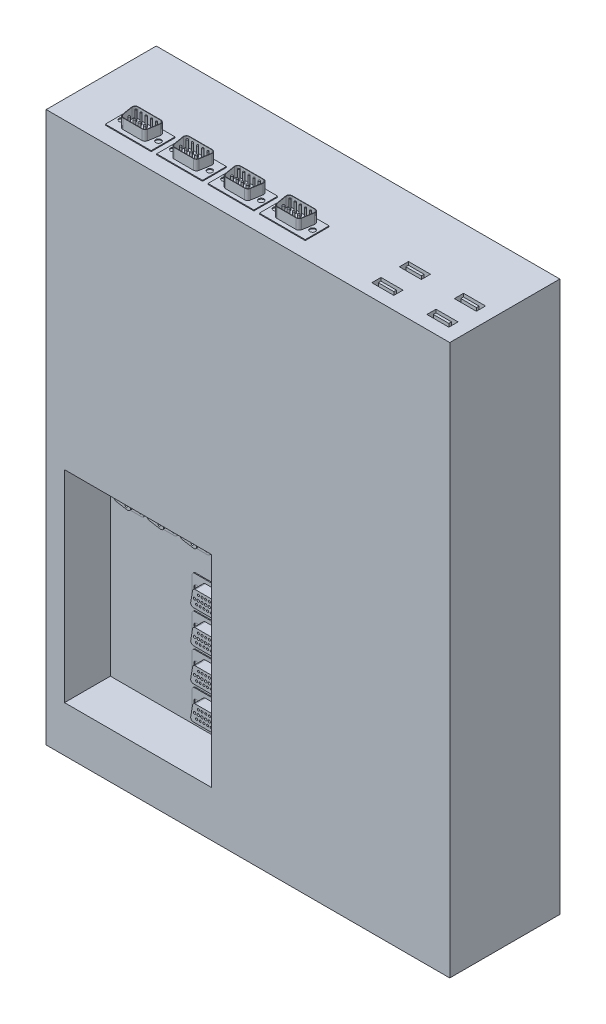
SolidWorks part; units mm, degrees
ref_plane "前视基准面" through (0, 0, 0) normal (0, 0, 1) x (1, 0, 0)
ref_plane "上视基准面" through (0, 0, 0) normal (0, 1, 0) x (1, 0, 0)
ref_plane "右视基准面" through (0, 0, 0) normal (1, 0, 0) x (0, 0, -1)
sketch "草图1" plane through (0, 0, 0) normal (0, 0, 1) x (1, 0, 0)
  line L1 (-110, -150) -> (110, -150)
  line L2 (-110, -150) -> (-110, 150)
  line L3 (-110, 150) -> (110, 150)
  line L4 (110, -150) -> (110, 150)
  line L5 (-110, -150) -> (110, 150) construction
  line L6 (-110, 150) -> (110, -150) construction
  point P0 (0, 0)
  dimension "D1" = 220
  dimension "D2" = 300
extrude "凸台-拉伸1" add sketch "草图1" along normal blind 60
sketch "草图2" plane through (0, 0, 60) normal (0, 0, 1) x (1, 0, 0)
  line L0 (-110, -150) -> (110, -150) construction
  line L1 (-100, -125) -> (-20, -125)
  line L2 (-100, -125) -> (-100, -15)
  line L3 (-100, -15) -> (-20, -15)
  line L4 (-20, -125) -> (-20, -15)
  line L5 (-110, 150) -> (-110, -150) construction
  dimension "D1" = 80
  dimension "D2" = 110
  dimension "D3" = 25
  dimension "D4" = 10
extrude "切除-拉伸1" cut sketch "草图2" against normal blind 25
sketch "草图3" plane through (0, 0, 35) normal (0, 0, 1) x (1, 0, 0)
  line L1 (-49, -55) -> (-29, -55)
  line L2 (-49, -55) -> (-50.5, -64)
  line L3 (-50.5, -64) -> (-27.5, -64)
  line L4 (-29, -55) -> (-27.5, -64)
  line L5 (-20, -15) -> (-100, -15) construction
  circle A0 centre (-46.0182, -56.8598) radius 0.5665
  circle A1 centre (-44.0182, -56.8598) radius 0.5665
  circle A2 centre (-42.0182, -56.8598) radius 0.5665
  circle A3 centre (-40.0182, -56.8598) radius 0.5665
  circle A4 centre (-38.0182, -56.8598) radius 0.5665
  circle A5 centre (-36.0182, -56.8598) radius 0.5665
  circle A6 centre (-34.0182, -56.8598) radius 0.5665
  circle A7 centre (-32.0182, -56.8598) radius 0.5665
  circle A8 centre (-48.0995, -59.4648) radius 0.6669
  circle A9 centre (-46.0995, -59.4648) radius 0.6669
  circle A10 centre (-44.0995, -59.4648) radius 0.6669
  circle A11 centre (-42.0995, -59.4648) radius 0.6669
  circle A12 centre (-40.0995, -59.4648) radius 0.6669
  circle A13 centre (-38.0995, -59.4648) radius 0.6669
  circle A14 centre (-36.0995, -59.4648) radius 0.6669
  circle A15 centre (-34.0995, -59.4648) radius 0.6669
  circle A16 centre (-32.0995, -59.4648) radius 0.6669
  circle A17 centre (-47.0252, -61.8014) radius 0.5541
  circle A18 centre (-45.0252, -61.8014) radius 0.5541
  circle A19 centre (-43.0252, -61.8014) radius 0.5541
  circle A20 centre (-41.0252, -61.8014) radius 0.5541
  circle A21 centre (-39.0252, -61.8014) radius 0.5541
  circle A22 centre (-37.0252, -61.8014) radius 0.5541
  circle A23 centre (-35.0252, -61.8014) radius 0.5541
  circle A24 centre (-33.0252, -61.8014) radius 0.5541
  circle A25 centre (-31.0252, -61.8014) radius 0.5541
  dimension "D1" = 20
  dimension "D2" = 9
  dimension "D3" = 23
  dimension "D4" = 40
  dimension "D5" = 1.5
  dimension "D6" = 8
  dimension "D7" = 9
  dimension "D8" = 9
extrude "凸台-拉伸2" add sketch "草图3" along normal blind 6
sketch "草图4" plane through (0, 0, 35) normal (0, 0, 1) x (1, 0, 0)
  line L0 (-39, -55) -> (-39, -64) construction
  line L1 (-55, -66) -> (-23, -66)
  line L2 (-55, -66) -> (-55, -53)
  line L3 (-55, -53) -> (-23, -53)
  line L4 (-23, -66) -> (-23, -53)
  line L5 (-55, -66) -> (-23, -53) construction
  line L6 (-55, -53) -> (-23, -66) construction
  line L7 (-29, -55) -> (-49, -55) construction
  line L8 (-50.5, -64) -> (-27.5, -64) construction
  line L9 (-49.75, -59.5) -> (-28.25, -59.5) construction
  line L10 (-49, -55) -> (-50.5, -64) construction
  line L11 (-27.5, -64) -> (-29, -55) construction
  circle A0 centre (-52.5, -59.5) radius 1.5
  circle A1 centre (-25.5, -59.5) radius 1.5
  point P0 (-39, -59.5)
  dimension "D5" = 3
  dimension "D6" = 3
  dimension "D1" = 13
  dimension "D2" = 32
  dimension "D3" = 2.5
  dimension "D4" = 2.5
extrude "凸台-拉伸3" add sketch "草图4" along normal blind 0.5
fillet "圆角2" radius 1.5 8 edges at (-27.5, -64, 38.25) (-50.5, -64, 38.25) (-29, -55, 38.25) (-49, -55, 38.25) (-23, -53, 35.25) (-23, -66, 35.25) (-55, -66, 35.25) (-55, -53, 35.25)
pattern_linear "阵列(线性)1" count 4 spacing 18 along (0, -1, 0) of "凸台-拉伸2", "凸台-拉伸3", "圆角2"
sketch "草图5" plane through (0, 0, 35) normal (0, 0, 1) x (1, 0, 0)
  line L0 (-83, -20.2354) -> (-92, -21.7354)
  line L1 (-92, -34.7354) -> (-83, -36.2354)
  line L2 (-92, -21.7354) -> (-92, -34.7354)
  line L3 (-100, -15) -> (-100, -125) construction
  line L4 (-83, -20.2354) -> (-83, -36.2354)
  circle A0 centre (-89.4, -32.5292) radius 0.5921
  circle A1 centre (-89.4, -29.7292) radius 0.5921
  circle A2 centre (-89.4, -26.9292) radius 0.5921
  circle A3 centre (-89.4, -24.1292) radius 0.5921
  circle A4 centre (-85.3806, -34.2588) radius 0.6355
  circle A5 centre (-85.3806, -31.4588) radius 0.6355
  circle A6 centre (-85.3806, -28.6588) radius 0.6355
  circle A7 centre (-85.3806, -25.8588) radius 0.6355
  circle A8 centre (-85.3806, -23.0588) radius 0.6355
  dimension "D1" = 9
  dimension "D2" = 16
  dimension "D3" = 13
  dimension "D4" = 1.5
  dimension "D7" = 8
  dimension "D8" = 2.6
  dimension "D9" = 4.0194
  dimension "D5" = 4
  dimension "D6" = 5
extrude "凸台-拉伸4" add sketch "草图5" along normal blind 6
sketch "草图6" plane through (0, 0, 35) normal (0, 0, 1) x (1, 0, 0)
  line L0 (-87.5, -20.9854) -> (-87.5, -35.4854) construction
  line L1 (-94, -40.7354) -> (-81, -40.7354)
  line L2 (-94, -40.7354) -> (-94, -15.7354)
  line L3 (-94, -15.7354) -> (-81, -15.7354)
  line L4 (-81, -40.7354) -> (-81, -15.7354)
  line L5 (-94, -40.7354) -> (-81, -15.7354) construction
  line L6 (-94, -15.7354) -> (-81, -40.7354) construction
  line L7 (-83, -20.2354) -> (-92, -21.7354) construction
  line L8 (-92, -34.7354) -> (-83, -36.2354) construction
  circle A0 centre (-83.3624, -18.2354) radius 1.5
  circle A1 centre (-83.3624, -38.2354) radius 1.5
  point P0 (-87.5, -28.2354)
  dimension "D3" = 3
  dimension "D4" = 3
  dimension "D6" = 2.5
  dimension "D1" = 13
  dimension "D2" = 25
  dimension "D5" = 2.5
extrude "凸台-拉伸5" add sketch "草图6" along normal blind 0.5
fillet "圆角3" radius 1.5 8 edges at (-94, -15.7354, 35.25) (-94, -40.7354, 35.25) (-81, -40.7354, 35.25) (-81, -15.7354, 35.25) (-83, -20.2354, 38.25) (-83, -36.2354, 38.25) (-92, -34.7354, 38.25) (-92, -21.7354, 38.25)
pattern_linear "阵列(线性)2" count 4 spacing 18 along (1, 0, 0) of "圆角3", "凸台-拉伸5", "凸台-拉伸4"
sketch "草图7" plane through (0, 150, 0) normal (0, 1, 0) x (1, 0, 0)
  line L0 (110, -60) -> (110, 0) construction
  line L1 (-2.5, -38.2759) -> (22.5, -38.2759)
  line L2 (-2.5, -38.2759) -> (-2.5, -51.2759)
  line L3 (-2.5, -51.2759) -> (22.5, -51.2759)
  line L4 (22.5, -38.2759) -> (22.5, -51.2759)
  line L5 (-2.5, -38.2759) -> (22.5, -51.2759) construction
  line L6 (-2.5, -51.2759) -> (22.5, -38.2759) construction
  circle A0 centre (0, -44.7759) radius 1.5
  circle A1 centre (20, -44.7759) radius 1.5
  point P0 (10, -44.7759)
  dimension "D5" = 3
  dimension "D6" = 3
  dimension "D1" = 25
  dimension "D2" = 13
  dimension "D3" = 2.5
  dimension "D4" = 2.5
  dimension "D7" = 100
extrude "凸台-拉伸6" add sketch "草图7" along normal blind 0.5
sketch "草图8" plane through (0, 150.5, 0) normal (0, 1, 0) x (1, 0, 0)
  line L0 (10, -38.2759) -> (10, -51.2759) construction
  line L1 (4.7707, -48.8104) -> (15.2293, -48.8104)
  line L2 (2.2911, -41.557) -> (3.2911, -47.557)
  line L3 (3.7707, -39.8104) -> (16.2293, -39.8104)
  line L4 (17.7089, -41.557) -> (16.7089, -47.557)
  line L5 (3.5, -48.8104) -> (18, -39.8104) construction
  line L6 (2, -39.8104) -> (16.5, -48.8104) construction
  line L7 (22.5, -38.2759) -> (-2.5, -38.2759) construction
  line L8 (-2.5, -51.2759) -> (22.5, -51.2759) construction
  line L9 (3.7707, -39.6104) -> (16.2293, -39.6104)
  line L10 (17.9062, -41.5899) -> (16.9062, -47.5899)
  line L11 (4.7707, -49.0104) -> (15.2293, -49.0104)
  line L12 (2.0938, -41.5899) -> (3.0938, -47.5899)
  line L13 (-2.5, -38.2759) -> (-2.5, -51.2759) construction
  arc A0 (4.7707, -48.8104) -> (3.2911, -47.557) centre (4.7707, -47.3104) cw
  arc A1 (15.2293, -48.8104) -> (16.7089, -47.557) centre (15.2293, -47.3104) ccw
  arc A2 (17.7089, -41.557) -> (16.2293, -39.8104) centre (16.2293, -41.3104) ccw
  arc A3 (2.2911, -41.557) -> (3.7707, -39.8104) centre (3.7707, -41.3104) cw
  arc A4 (17.9062, -41.5899) -> (16.2293, -39.6104) centre (16.2293, -41.3104) ccw
  arc A5 (15.2293, -49.0104) -> (16.9062, -47.5899) centre (15.2293, -47.3104) ccw
  arc A6 (4.7707, -49.0104) -> (3.0938, -47.5899) centre (4.7707, -47.3104) cw
  arc A7 (2.0938, -41.5899) -> (3.7707, -39.6104) centre (3.7707, -41.3104) cw
  circle A8 centre (4.5, -41.557) radius 0.4335
  circle A9 centre (7.3, -41.557) radius 0.4335
  circle A10 centre (10.1, -41.557) radius 0.4335
  circle A11 centre (12.9, -41.557) radius 0.4335
  circle A12 centre (15.7, -41.557) radius 0.4335
  circle A13 centre (5.9, -46.5696) radius 0.5421
  circle A14 centre (8.7, -46.5696) radius 0.5421
  circle A15 centre (11.5, -46.5696) radius 0.5421
  circle A16 centre (14.3, -46.5696) radius 0.5421
  point P0 (10, -44.7759)
  dimension "D5" = 1.5
  dimension "D1" = 16
  dimension "D2" = 9
  dimension "D3" = 13
  dimension "D4" = 1.5
  dimension "D9" = 7
  dimension "D10" = 1.4
  dimension "D6" = 0.2
  dimension "D7" = 5
  dimension "D8" = 4
extrude "凸台-拉伸7" add sketch "草图8" along normal blind 5.5 contours A7 L12 A6 L11 A5 L10 A4 L9 L2 A3 L3 A2 L4 A1 L1 A0 | A8 | A9 | A10 | A11 | A12 | A16 | A15 | A14 | A13 region at (10, 150.5, 39.7948) region at (4.5, 150.5, 41.557) region at (7.3, 150.5, 41.557) region at (10.1, 150.5, 41.557) region at (12.9, 150.5, 41.557) region at (15.7, 150.5, 41.557) region at (5.9, 150.5, 46.5696) region at (8.7, 150.5, 46.5696) region at (11.5, 150.5, 46.5696) region at (14.3, 150.5, 46.5696)
pattern_linear "阵列(线性)3" count 4 spacing 28 along (-1, 0, 0) of "凸台-拉伸7", "凸台-拉伸6"
sketch "草图9" plane through (0, 150, 0) normal (0, 1, 0) x (1, 0, 0)
  line L1 (90.5013, -47.9894) -> (102.5013, -47.9894)
  line L2 (90.5013, -47.9894) -> (90.5013, -52.9894)
  line L3 (90.5013, -52.9894) -> (102.5013, -52.9894)
  line L4 (102.5013, -47.9894) -> (102.5013, -52.9894)
  line L5 (90.5013, -47.9894) -> (102.5013, -52.9894) construction
  line L6 (90.5013, -52.9894) -> (102.5013, -47.9894) construction
  line L7 (92.2511, -51.2048) -> (100.7515, -51.2048)
  line L8 (92.2511, -51.2048) -> (92.2511, -49.774)
  line L9 (92.2511, -49.774) -> (100.7515, -49.774)
  line L10 (100.7515, -51.2048) -> (100.7515, -49.774)
  line L11 (92.2511, -51.2048) -> (100.7515, -49.774) construction
  line L12 (92.2511, -49.774) -> (100.7515, -51.2048) construction
  point P0 (96.5013, -50.4894)
  point P5 (96.5013, -50.4894)
  dimension "D1" = 5
  dimension "D2" = 12
extrude "切除-拉伸2" cut sketch "草图9" against normal blind 15
pattern_linear "阵列(线性)4" count 2 spacing 15 along (0, 0, -1) count 2 spacing 30 along (-1, 0, 0) of "切除-拉伸2"
